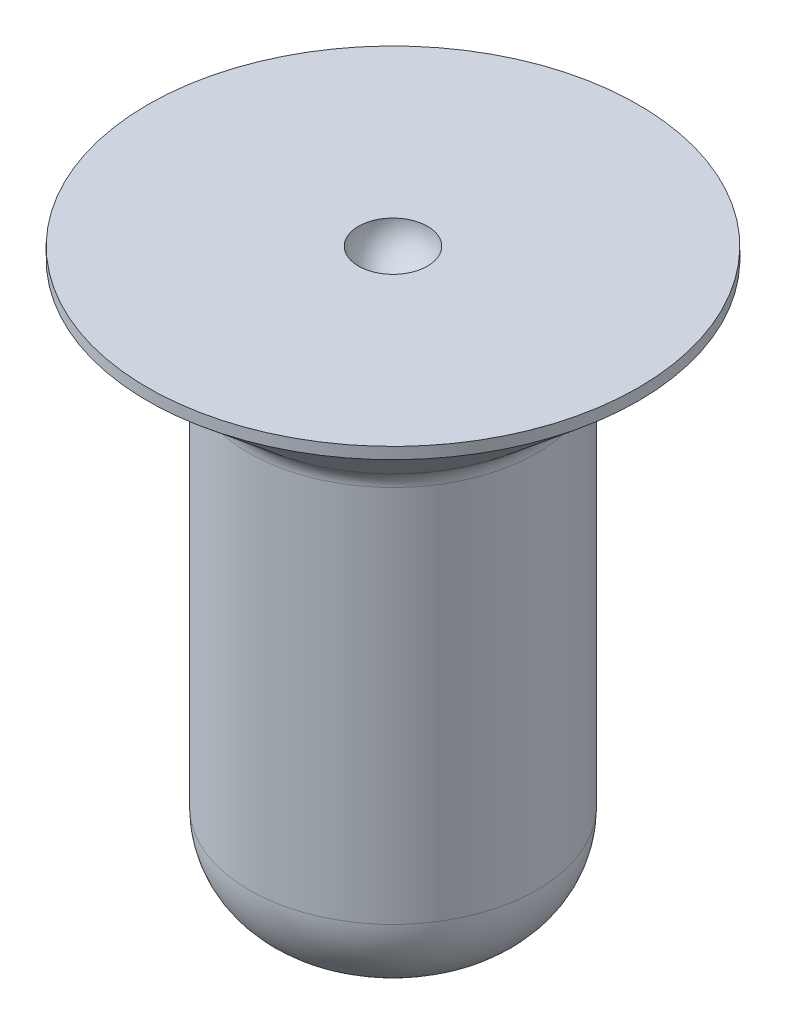
SolidWorks part; units mm, degrees
ref_plane "Front Plane" through (0, 0, 0) normal (0, 0, 1) x (1, 0, 0)
ref_plane "Top Plane" through (0, 0, 0) normal (0, 1, 0) x (1, 0, 0)
ref_plane "Right Plane" through (0, 0, 0) normal (1, 0, 0) x (0, 0, -1)
sketch "Sketch1" plane through (0, 0, 0) normal (0, 0, 1) x (1, 0, 0)
  line L0 (0, 28.4495) -> (0, -56.638) construction
  line L1 (0, -0.381) -> (0, -6.35)
  line L2 (0, -6.35) -> (0.5969, -6.35)
  line L3 (1.5875, -5.3594) -> (1.5875, -1.1841)
  line L4 (1.6782, -0.9895) -> (2.7061, -0.127)
  line L5 (2.7061, -0.127) -> (2.7061, 0)
  line L6 (2.7061, 0) -> (0.381, 0)
  arc A0 (0.5969, -6.35) -> (1.5875, -5.3594) centre (0.5969, -5.3594) ccw
  arc A1 (1.5875, -1.1841) -> (1.6782, -0.9895) centre (1.8415, -1.1841) cw
  arc A2 (0.381, 0) -> (0, -0.381) centre (0, 0) cw
  point P2 (2.8575, 0)
  dimension "D1" = 0.254
  dimension "T" = 0.9906
  dimension "D3" = 0.381
  dimension "A" = 5.715
  dimension "E" = 0.127
  dimension "LENGTH" = 6.35
  dimension "D2" = 50
  dimension "D" = 3.175
revolve "Revolve1" add sketch "Sketch1" angle 360 about L0
ref_axis "Axis1" through (0, 0.2388, 0) along (0, -1, 0)
